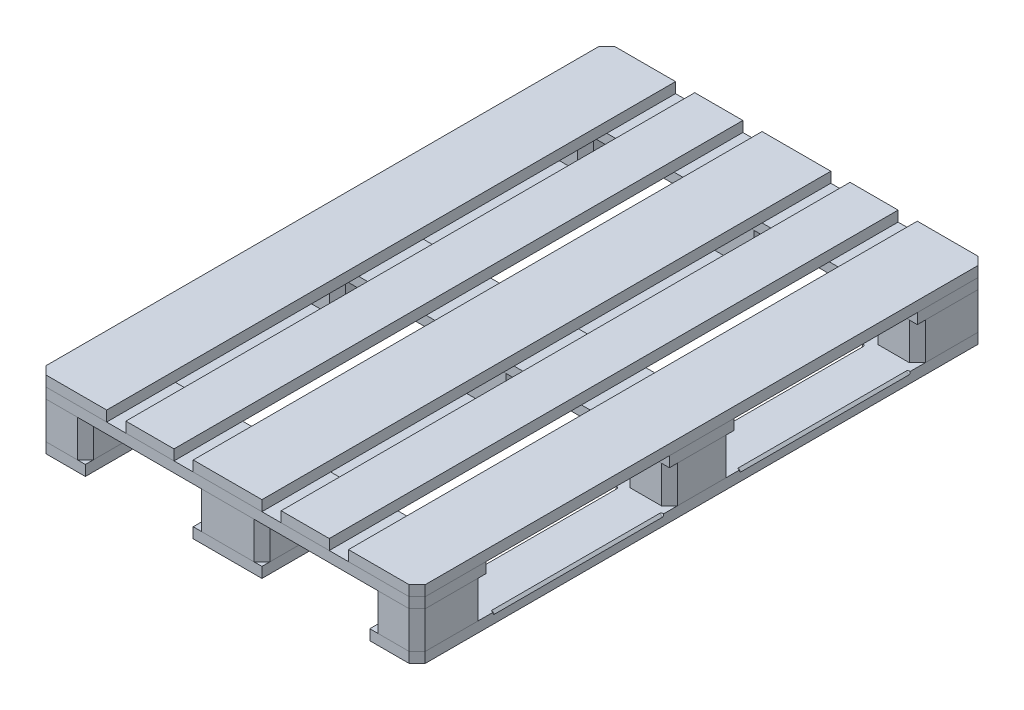
SolidWorks part; units mm, degrees
ref_plane "Front Plane" through (0, 0, 0) normal (0, 0, 1) x (1, 0, 0)
ref_plane "Top Plane" through (0, 0, 0) normal (0, 1, 0) x (1, 0, 0)
ref_plane "Right Plane" through (0, 0, 0) normal (1, 0, 0) x (0, 0, -1)
sketch "Sketch1" plane through (0, 0, 0) normal (0, 0, 1) x (1, 0, 0)
  line L0 (-400, 0) -> (400, 0) construction
  line L5 (-400, 72) -> (-400, -72) construction
  line L6 (400, 72) -> (400, -72) construction
  line L11 (-400, -72) -> (400, -72) construction
  line L12 (-400, 72) -> (400, 72) construction
  line L13 (-300, 72) -> (-300, -72) construction
  line L17 (0, 72) -> (0, -72) construction
  line L18 (-400, 0) -> (-300, 0)
  line L19 (400, 50) -> (400, 28) construction
  line L20 (400, 72) -> (400, 50) construction
  line L21 (300, 72) -> (300, -72) construction
  line L22 (-400, 50) -> (400, 50) construction
  line L23 (-400, -50) -> (400, -50) construction
  line L28 (72.5, -72) -> (-72.5, -72)
  line L29 (72.5, -72) -> (72.5, 72)
  line L30 (72.5, 72) -> (-72.5, 72)
  line L31 (-72.5, -72) -> (-72.5, 72)
  line L32 (72.5, -72) -> (-72.5, 72) construction
  line L33 (72.5, 72) -> (-72.5, -72) construction
  point P3 (0, 0)
  point P6 (-400, 0)
  point P9 (400, 0)
  point P23 (0, 0)
  point P32 (0, 0)
  dimension "D1" = 100
  dimension "Width" = 800
  dimension "D2" = 145
  dimension "Height" = 144
  dimension "D3" = 22
  dimension "Maximum Fork Height" = 100
sketch "Sketch2" plane through (0, 0, 0) normal (1, 0, 0) x (0, 0, -1)
  line L0 (600, 0) -> (-600, 0) construction
  point P0 (-455, 0)
  point P3 (-68, 0)
  point P4 (0, 0)
  point P5 (68, 0)
  point P7 (455, 0)
  dimension "Depth" = 1200
  dimension "D1" = 145
  dimension "D2" = 145
  dimension "Maximum Fork Width" = 387
  dimension "D3" = 387
sketch "Sketch3" plane through (0, 0, 0) normal (0, 0, 1) x (1, 0, 0)
  line L0 (-400, -50) -> (400, -50) construction
  line L36 (-400, 72) -> (-400, -72) construction
  line L37 (-300, 72) -> (-300, -72) construction
  line L38 (-400, -72) -> (-300, -72)
  line L39 (-400, -72) -> (-400, -50)
  line L40 (-400, -50) -> (-300, -50)
  line L41 (-300, -72) -> (-300, -50)
  line L43 (72.5, -72) -> (72.5, 72) construction
  line L44 (72.5, -72) -> (-72.5, -72)
  line L45 (72.5, -72) -> (72.5, -50)
  line L46 (72.5, -50) -> (-72.5, -50)
  line L47 (-72.5, -72) -> (-72.5, -50)
  line L48 (-72.5, -72) -> (-72.5, 72) construction
  line L50 (400, -50) -> (300, -50)
  line L51 (400, -50) -> (400, -72)
  line L52 (400, -72) -> (300, -72)
  line L53 (300, -50) -> (300, -72)
  line L54 (300, 72) -> (300, -72) construction
  line L55 (400, 72) -> (400, -72) construction
extrude "Boss-Extrude1" add sketch "Sketch3" along normal up to vertex (600 mm away) and the other way up to vertex (600 mm away) up to point (0, 0, 600) other way up to point (0, 0, -600)
sketch "Sketch4" plane through (0, -50, 0) normal (0, 1, 0) x (1, 0, 0)
  line L0 (72.5, -600) -> (72.5, 600) construction
  line L1 (-55.5, -600) -> (55.5, -600)
  line L2 (-72.5, -583) -> (-72.5, -472)
  line L3 (-55.5, -455) -> (55.5, -455)
  line L4 (72.5, -583) -> (72.5, -472)
  line L5 (-72.5, -600) -> (-72.5, 600) construction
  line L6 (55.5, 600) -> (-55.5, 600)
  line L7 (72.5, 583) -> (72.5, 472)
  line L8 (55.5, 455) -> (-55.5, 455)
  line L9 (-72.5, 583) -> (-72.5, 472)
  line L10 (300, -600) -> (300, 600) construction
  line L11 (383, 600) -> (317, 600)
  line L12 (400, 583) -> (400, 472)
  line L13 (383, 455) -> (317, 455)
  line L14 (300, 583) -> (300, 472)
  line L15 (-400, -600) -> (-400, 600) construction
  line L16 (-55.5, 68) -> (55.5, 68)
  line L17 (-72.5, 51) -> (-72.5, -51)
  line L18 (-55.5, -68) -> (55.5, -68)
  line L19 (72.5, 51) -> (72.5, -51)
  line L20 (-317, 600) -> (-383, 600)
  line L21 (-300, 583) -> (-300, 472)
  line L22 (-317, 455) -> (-383, 455)
  line L23 (-400, 583) -> (-400, 472)
  line L24 (-300, -600) -> (-300, 600) construction
  line L25 (-383, -600) -> (-317, -600)
  line L26 (-400, -583) -> (-400, -472)
  line L27 (-383, -455) -> (-317, -455)
  line L28 (-300, -583) -> (-300, -472)
  line L29 (400, -600) -> (400, 600) construction
  line L30 (317, -600) -> (383, -600)
  line L31 (300, -583) -> (300, -472)
  line L32 (317, -455) -> (383, -455)
  line L33 (400, -583) -> (400, -472)
  line L34 (-400, -472) -> (-383, -455)
  line L35 (383, 68) -> (317, 68)
  line L36 (400, 51) -> (400, -51)
  line L37 (383, -68) -> (317, -68)
  line L38 (300, 51) -> (300, -51)
  line L39 (-317, 68) -> (-383, 68)
  line L40 (-300, 51) -> (-300, -51)
  line L41 (-317, -68) -> (-383, -68)
  line L42 (-400, 51) -> (-400, -51)
  line L43 (-317, -600) -> (-300, -583)
  line L44 (-400, -583) -> (-383, -600)
  line L45 (-317, -455) -> (-300, -472)
  line L46 (-72.5, -472) -> (-55.5, -455)
  line L47 (55.5, -455) -> (72.5, -472)
  line L48 (55.5, -600) -> (72.5, -583)
  line L49 (-72.5, -583) -> (-55.5, -600)
  line L50 (300, -472) -> (317, -455)
  line L51 (383, -455) -> (400, -472)
  line L52 (383, -600) -> (400, -583)
  line L53 (300, -583) -> (317, -600)
  line L54 (400, 51) -> (383, 68)
  line L55 (317, 68) -> (300, 51)
  line L56 (317, -68) -> (300, -51)
  line L57 (400, -51) -> (383, -68)
  line L58 (55.5, 68) -> (72.5, 51)
  line L59 (-72.5, 51) -> (-55.5, 68)
  line L60 (-72.5, -51) -> (-55.5, -68)
  line L61 (55.5, -68) -> (72.5, -51)
  line L62 (-383, 68) -> (-400, 51)
  line L63 (-383, -68) -> (-400, -51)
  line L64 (-300, -51) -> (-317, -68)
  line L65 (-300, 51) -> (-317, 68)
  line L66 (-300, 583) -> (-317, 600)
  line L67 (-383, 600) -> (-400, 583)
  line L68 (-383, 455) -> (-400, 472)
  line L69 (-300, 472) -> (-317, 455)
  line L70 (-55.5, 600) -> (-72.5, 583)
  line L71 (72.5, 583) -> (55.5, 600)
  line L72 (72.5, 472) -> (55.5, 455)
  line L73 (-55.5, 455) -> (-72.5, 472)
  line L74 (317, 455) -> (300, 472)
  line L75 (400, 472) -> (383, 455)
  line L76 (400, 583) -> (383, 600)
  line L77 (317, 600) -> (300, 583)
  point P0 (-72.5, -600)
  point P1 (72.5, -455)
  point P2 (-72.5, -455)
  point P3 (72.5, -600)
  point P7 (72.5, 600)
  point P9 (-72.5, 455)
  point P10 (72.5, 455)
  point P11 (-72.5, 600)
  point P17 (400, 600)
  point P18 (300, 455)
  point P19 (400, 455)
  point P20 (300, 600)
  point P23 (-72.5, 68)
  point P24 (72.5, -68)
  point P25 (-72.5, -68)
  point P26 (72.5, 68)
  point P27 (-300, 600)
  point P30 (-400, 455)
  point P31 (-300, 455)
  point P32 (-400, 600)
  point P36 (-400, -600)
  point P37 (-300, -455)
  point P38 (-400, -455)
  point P39 (-300, -600)
  point P43 (300, -600)
  point P44 (400, -455)
  point P45 (300, -455)
  point P46 (400, -600)
  point P50 (400, 68)
  point P51 (300, -68)
  point P52 (400, -68)
  point P53 (300, 68)
  point P54 (-300, 68)
  point P55 (-400, -68)
  point P56 (-300, -68)
  point P57 (-400, 68)
extrude "Boss-Extrude2" add sketch "Sketch4" along normal up to vertex (78 mm away) separate body up to point (400, 28, 0)
sketch "Sketch5" plane through (0, 28, 0) normal (0, 1, 0) x (1, 0, 0)
  line L0 (-400, -600) -> (-400, 600) construction
  line L1 (-400, -600) -> (400, -600)
  line L2 (-400, -600) -> (-400, -455)
  line L3 (-400, -455) -> (400, -455)
  line L4 (400, -600) -> (400, -455)
  line L5 (-400, -68) -> (400, -68)
  line L6 (-400, -68) -> (-400, 68)
  line L7 (-400, 68) -> (400, 68)
  line L8 (400, -68) -> (400, 68)
  line L9 (-400, 455) -> (400, 455)
  line L10 (-400, 455) -> (-400, 600)
  line L11 (-400, 600) -> (400, 600)
  line L12 (400, 455) -> (400, 600)
  line L13 (-383, 455) -> (-317, 455) construction
  line L14 (-383, -68) -> (-317, -68) construction
  line L15 (400, -600) -> (400, 600) construction
  line L16 (383, 68) -> (317, 68) construction
  line L17 (383, -455) -> (317, -455) construction
extrude "Boss-Extrude3" add sketch "Sketch5" along normal up to vertex (22 mm away) separate body up to point (-400, 50, 0)
sketch "Sketch6" plane through (0, 50, 0) normal (0, 1, 0) x (1, 0, 0)
  line L0 (-400, -600) -> (400, -600) construction
  line L1 (72.5, 600) -> (-72.5, 600)
  line L2 (72.5, 600) -> (72.5, -600)
  line L3 (72.5, -600) -> (-72.5, -600)
  line L4 (-72.5, 600) -> (-72.5, -600)
  line L5 (-400, 600) -> (-255, 600)
  line L6 (-400, 600) -> (-400, -600)
  line L7 (-400, -600) -> (-255, -600)
  line L8 (-255, 600) -> (-255, -600)
  line L9 (400, 455) -> (400, 600) construction
  line L10 (255, -600) -> (400, -600)
  line L11 (255, -600) -> (255, 600)
  line L12 (255, 600) -> (400, 600)
  line L13 (400, -600) -> (400, 600)
  line L14 (400, 600) -> (-400, 600) construction
  line L15 (72.5, 600) -> (113, 600) construction
  line L16 (113, 600) -> (214.5, 600)
  line L17 (113, 600) -> (113, -600)
  line L18 (113, -600) -> (214.5, -600)
  line L19 (214.5, 600) -> (214.5, -600)
  line L20 (-214.5, -600) -> (-113, -600)
  line L21 (-214.5, -600) -> (-214.5, 600)
  line L22 (-214.5, 600) -> (-113, 600)
  line L23 (-113, -600) -> (-113, 600)
  line L24 (214.5, 600) -> (255, 600) construction
  line L25 (-255, 600) -> (-214.5, 600) construction
  line L26 (-113, 600) -> (-72.5, 600) construction
  line L27 (72.5, -600) -> (72.5, 600) construction
  line L28 (-72.5, -600) -> (-72.5, 600) construction
  dimension "D1" = 287
extrude "Boss-Extrude4" add sketch "Sketch6" along normal up to vertex (22 mm away) separate body up to point (400, 72, 0)
sketch "Sketch7" plane through (0, -50, 0) normal (0, 1, 0) x (1, 0, 0)
  line L0 (383, -600) -> (400, -583)
  line L1 (400, -583) -> (400, -600)
  line L2 (400, -600) -> (383, -600)
  line L3 (400, 583) -> (383, 600)
  line L4 (383, 600) -> (400, 600)
  line L5 (400, 600) -> (400, 583)
  line L6 (-400, 600) -> (-383, 600)
  line L7 (-383, 600) -> (-400, 583)
  line L8 (-400, 583) -> (-400, 600)
  line L9 (-400, -583) -> (-400, -600)
  line L10 (-400, -600) -> (-383, -600)
  line L11 (-383, -600) -> (-400, -583)
extrude "Cut-Extrude1" cut sketch "Sketch7" against normal through all both and the other way through all
sketch "Sketch8" plane through (0, 0, 0) normal (0, 0, 1) x (1, 0, 0)
  line L0 (400, -55) -> (395, -50)
  line L1 (400, 72) -> (400, -72) construction
  line L2 (-400, -50) -> (400, -50) construction
  line L3 (395, -50) -> (400, -50)
  line L4 (400, -50) -> (400, -55)
  line L5 (300, -50) -> (305, -50)
  line L6 (305, -50) -> (300, -55)
  line L7 (300, 72) -> (300, -72) construction
  line L8 (300, -55) -> (300, -50)
  line L9 (67.5, -50) -> (72.5, -50)
  line L10 (72.5, -50) -> (72.5, -55)
  line L11 (72.5, -72) -> (72.5, 72) construction
  line L12 (72.5, -55) -> (67.5, -50)
  line L13 (0, -50) -> (0, -72) construction
  line L14 (-72.5, -55) -> (-67.5, -50)
  line L15 (-72.5, -50) -> (-72.5, -55)
  line L16 (-67.5, -50) -> (-72.5, -50)
  line L17 (-300, -55) -> (-300, -50)
  line L18 (-305, -50) -> (-300, -55)
  line L19 (-300, -50) -> (-305, -50)
  line L20 (-400, -50) -> (-400, -55)
  line L21 (-395, -50) -> (-400, -50)
  line L22 (-400, -55) -> (-395, -50)
  dimension "D1" = 5
extrude "Cut-Extrude2" cut sketch "Sketch8" along normal blind 360 from offset 80
extrude "Cut-Extrude3" cut sketch "Sketch8<2>" against normal blind 360 from offset 80 offset against normal yes
sketch "Sketch8<2>" plane through (0, 0, 0) normal (0, 0, 1) x (1, 0, 0) same geometry as "Sketch8"
fillet "Fillet1" radius 3 8 edges at (302.5, -52.5, 80) (302.5, -52.5, 440) (302.5, -52.5, -80) (302.5, -52.5, -440) (397.5, -52.5, -440) (397.5, -52.5, -80) (397.5, -52.5, 440) (397.5, -52.5, 80)
fillet "Fillet2" radius 3 8 edges at (-70, -52.5, -80) (-70, -52.5, -440) (70, -52.5, -440) (70, -52.5, -80) (-70, -52.5, 80) (-70, -52.5, 440) (70, -52.5, 440) (70, -52.5, 80)
fillet "Fillet3" radius 3 8 edges at (-397.5, -52.5, 440) (-302.5, -52.5, 80) (-302.5, -52.5, 440) (-397.5, -52.5, 80) (-397.5, -52.5, -80) (-302.5, -52.5, -80) (-302.5, -52.5, -440) (-397.5, -52.5, -440)
equation "\"D3@Sketch2\"=\"Maximum Fork Width@Sketch2\""
